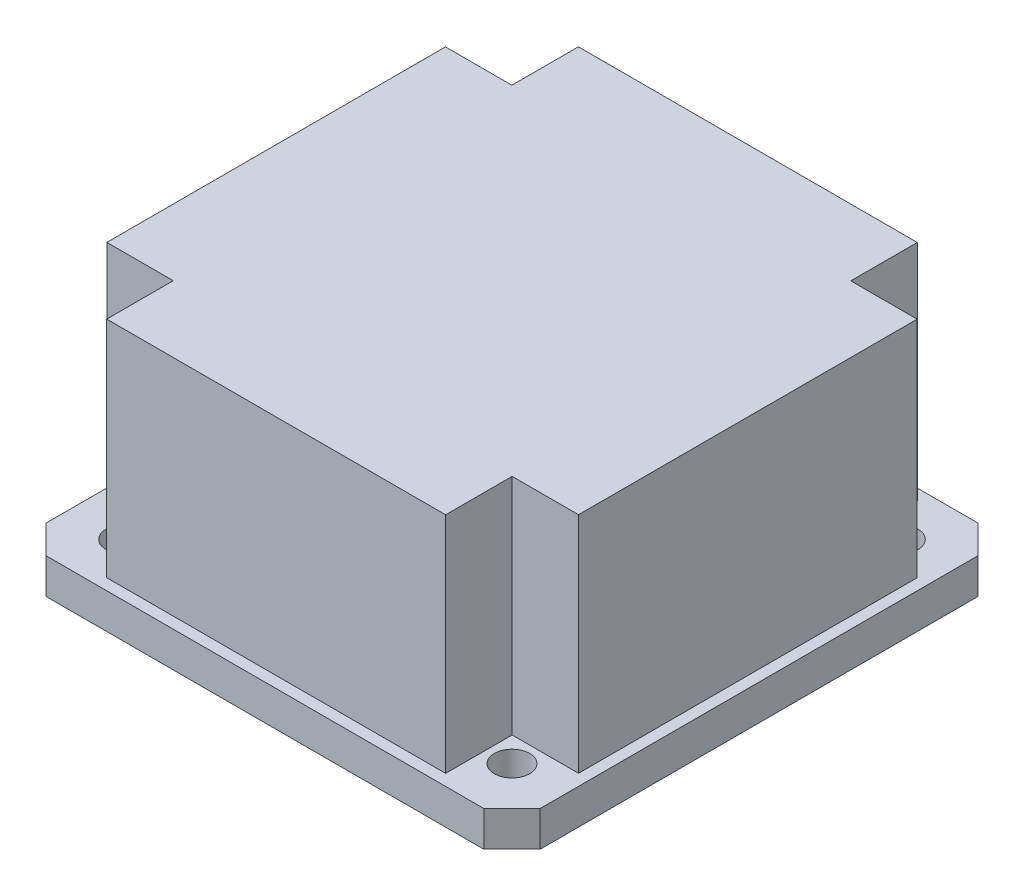
SolidWorks part; units mm, degrees
ref_plane "Front Plane" through (0, 0, 0) normal (0, 0, 1) x (1, 0, 0)
ref_plane "Top Plane" through (0, 0, 0) normal (0, 1, 0) x (1, 0, 0)
ref_plane "Right Plane" through (0, 0, 0) normal (1, 0, 0) x (0, 0, -1)
sketch "Sketch2" plane through (0, 0, 0) normal (0, 1, 0) x (1, 0, 0)
  line L1 (-22.225, -22.225) -> (22.225, -22.225)
  line L2 (-22.225, -22.225) -> (-22.225, 22.225)
  line L3 (-22.225, 22.225) -> (22.225, 22.225)
  line L4 (22.225, -22.225) -> (22.225, 22.225)
  line L5 (-22.225, -22.225) -> (22.225, 22.225) construction
  line L6 (-22.225, 22.225) -> (22.225, -22.225) construction
  point P0 (0, 0)
  dimension "D1" = 44.45
  dimension "D2" = 44.45
extrude "Boss-Extrude1" add sketch "Sketch2" along normal blind 3.175
chamfer "Chamfer1" distance 2.54 angle 45 4 edges at (22.225, 1.5875, -22.225) (22.225, 1.5875, 22.225) (-22.225, 1.5875, 22.225) (-22.225, 1.5875, -22.225)
sketch "Sketch3" plane through (0, 3.175, 0) normal (0, 1, 0) x (1, 0, 0)
  line L0 (0, 22.225) -> (0, -22.225) construction
  line L1 (19.685, 22.225) -> (-19.685, 22.225) construction
  line L2 (-19.685, -22.225) -> (19.685, -22.225) construction
  line L3 (-22.225, 0) -> (22.225, 0) construction
  line L4 (-22.225, 19.685) -> (-22.225, -19.685) construction
  line L5 (22.225, -19.685) -> (22.225, 19.685) construction
  circle A0 centre (-17.4625, 17.4625) radius 1.5875
  dimension "D3" = 3.175
  dimension "D1" = 34.925
  dimension "D2" = 34.925
extrude "Cut-Extrude1" cut sketch "Sketch3" against normal through all
mirror "Mirror1" about plane through (0, 0, 0) normal (1, 0, 0) of "Cut-Extrude1"
mirror "Mirror2" about plane through (0, 0, 0) normal (0, 0, 1) of "Mirror1"
sketch "Sketch4" plane through (0, 3.175, 0) normal (0, 1, 0) x (1, 0, 0)
  line L1 (-21.209, -21.209) -> (21.209, -21.209)
  line L2 (-21.209, -21.209) -> (-21.209, 21.209)
  line L3 (-21.209, 21.209) -> (21.209, 21.209)
  line L4 (21.209, -21.209) -> (21.209, 21.209)
  line L5 (-21.209, -21.209) -> (21.209, 21.209) construction
  line L6 (-21.209, 21.209) -> (21.209, -21.209) construction
  point P0 (0, 0)
  dimension "D1" = 42.418
  dimension "D2" = 42.418
extrude "Boss-Extrude2" add sketch "Sketch4" along normal blind 20.1422
sketch "Sketch5" plane through (0, 23.3172, 0) normal (0, 1, 0) x (1, 0, 0)
  line L5 (-21.209, 21.209) -> (-15.24, 21.209)
  line L6 (-21.209, 21.209) -> (-21.209, 15.2273)
  line L7 (-21.209, 15.2273) -> (-15.24, 15.2273)
  line L8 (-15.24, 21.209) -> (-15.24, 15.2273)
  dimension "D1" = 5.969
  dimension "D2" = 5.9817
extrude "Cut-Extrude2" cut sketch "Sketch5" against normal up to surface (20.1422 mm away) up to face at (0, 3.175, -21.717)
mirror "Mirror3" about plane through (0, 0, 0) normal (1, 0, 0) of "Cut-Extrude2" second plane through (0, 0, 0) second plane normal (0, 0, 1)
